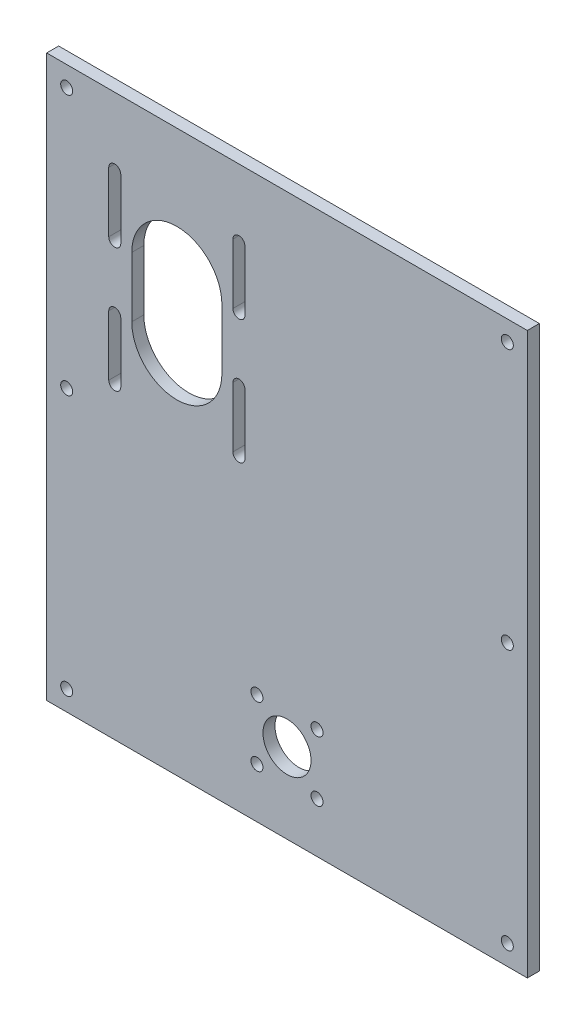
SolidWorks part; units mm, degrees
ref_plane "Plan de face" through (0, 0, 0) normal (0, 0, 1) x (1, 0, 0)
ref_plane "Plan de dessus" through (0, 0, 0) normal (0, 1, 0) x (1, 0, 0)
ref_plane "Plan de droite" through (0, 0, 0) normal (1, 0, 0) x (0, 0, -1)
sketch "Esquisse1" plane through (0, 0, 0) normal (0, 0, 1) x (1, 0, 0)
  line L0 (-27.5, 27.5) -> (-27.5, 42.5) construction
  line L1 (60, -75) -> (-60, -75)
  line L2 (60, -75) -> (60, 75)
  line L3 (60, 75) -> (-60, 75)
  line L4 (-60, -75) -> (-60, 75)
  line L5 (60, -75) -> (-60, 75) construction
  line L6 (60, 75) -> (-60, -75) construction
  line L9 (60, -65) -> (50, -65)
  line L10 (50, -75) -> (50, -65)
  line L13 (-60, -65) -> (-50, -65)
  line L14 (-50, -75) -> (-50, -65)
  line L15 (-38.75, 27.5) -> (-38.75, 42.5)
  line L16 (-16.25, 27.5) -> (-16.25, 42.5)
  line L17 (-43, 43) -> (-43, 58) construction
  line L18 (-44.5, 43) -> (-44.5, 58)
  line L19 (-41.5, 43) -> (-41.5, 58)
  line L20 (-43, 12) -> (-43, 27) construction
  line L21 (-44.5, 12) -> (-44.5, 27)
  line L22 (-41.5, 12) -> (-41.5, 27)
  line L23 (-27.5, 75) -> (-27.5, -75) construction
  line L24 (-27.5, 53.75) -> (-27.5, 16.25) construction
  line L27 (-12, 12) -> (-12, 27) construction
  line L30 (-10.5, 12) -> (-10.5, 27)
  line L31 (-13.5, 12) -> (-13.5, 27)
  line L32 (-12, 43) -> (-12, 58) construction
  line L33 (-10.5, 43) -> (-10.5, 58)
  line L34 (-13.5, 43) -> (-13.5, 58)
  arc A0 (-38.75, 27.5) -> (-16.25, 27.5) centre (-27.5, 27.5) ccw
  arc A1 (-16.25, 42.5) -> (-38.75, 42.5) centre (-27.5, 42.5) ccw
  arc A2 (-44.5, 43) -> (-41.5, 43) centre (-43, 43) ccw
  arc A3 (-41.5, 58) -> (-44.5, 58) centre (-43, 58) ccw
  arc A4 (-44.5, 12) -> (-41.5, 12) centre (-43, 12) ccw
  arc A5 (-41.5, 27) -> (-44.5, 27) centre (-43, 27) ccw
  arc A10 (-10.5, 12) -> (-13.5, 12) centre (-12, 12) cw
  arc A11 (-13.5, 27) -> (-10.5, 27) centre (-12, 27) cw
  arc A12 (-10.5, 43) -> (-13.5, 43) centre (-12, 43) cw
  arc A13 (-13.5, 58) -> (-10.5, 58) centre (-12, 58) cw
  point P0 (0, 0)
  point P14 (-27.5, 35)
  point P21 (-43, 50.5)
  point P28 (-43, 19.5)
  point P37 (-12, 19.5)
  point P44 (-12, 50.5)
  dimension "D13" = 40
  dimension "D1" = 10
  dimension "D2" = 10
  dimension "D3" = 150
  dimension "D4" = 120
  dimension "D5" = 32.5
  dimension "D6" = 15.5
  dimension "D7" = 22.5
  dimension "D8" = 3
  dimension "D9" = 15.5
  dimension "D10" = 15
  dimension "D11" = 3
  dimension "D12" = 31
extrude "Boss.-Extru.1" add sketch "Esquisse1" along normal blind 3 contours L14 L1 L10 L9 L2 L3 L4 L13 A5 L22 A4 L21 A3 L19 A2 L18 A1 L16 A0 L15 L31 A11 L30 A10 L34 A13 L33 A12 region at (1.539, -1.1282, 0)
sketch "Esquisse2" plane through (0, 0, 3) normal (0, 0, 1) x (1, 0, 0)
  line L0 (-55, 75) -> (-55, -65) construction
  line L1 (60, 75) -> (-60, 75) construction
  line L2 (60, -65) -> (50, -65) construction
  line L3 (50, -70) -> (-50, -70) construction
  line L4 (50, -75) -> (50, -65) construction
  line L5 (-50, -75) -> (-50, -65) construction
  line L6 (0, 75) -> (0, -75) construction
  line L7 (50, -75) -> (-50, -75) construction
  circle A0 centre (45, -70) radius 1.5
  circle A3 centre (-55, -60) radius 1.5
  circle A4 centre (-55, 5) radius 1.5
  circle A5 centre (-55, 70) radius 1.5
  circle A9 centre (22.5, -70) radius 1.5
  circle A10 centre (0, -70) radius 1.5
  circle A11 centre (-22.5, -70) radius 1.5
  circle A12 centre (-45, -70) radius 1.5
  circle A13 centre (55, -60) radius 1.5
  circle A14 centre (55, 5) radius 1.5
  circle A15 centre (55, 70) radius 1.5
  dimension "D2" = 3
  dimension "D6" = 3
  dimension "D1" = 5
  dimension "D3" = 5
  dimension "D5" = 5
  dimension "D7" = 5
  dimension "D4" = 5
  dimension "D8" = 3
extrude "Enlèv. mat.-Extru.2" cut sketch "Esquisse2" against normal blind 3
sketch "Esquisse3" plane through (0, 0, 3) normal (0, 0, 1) x (1, 0, 0)
  line L3 (50, -75) -> (-50, -75) construction
  line L4 (0, 75) -> (0, -75) construction
  line L5 (60, 75) -> (-60, 75) construction
  line L6 (-7.5, -37.5) -> (7.5, -37.5) construction
  line L7 (7.5, -57.5) -> (-7.5, -57.5) construction
  line L8 (12.5, -52.5) -> (12.5, -37.5) construction
  line L9 (7.5, -32.5) -> (-7.5, -32.5) construction
  line L10 (-12.5, -52.5) -> (-12.5, -37.5) construction
  line L11 (12.5, -57.5) -> (-12.5, -32.5) construction
  line L12 (12.5, -32.5) -> (-12.5, -57.5) construction
  line L13 (-7.5, -37.5) -> (-7.5, -52.5) construction
  circle A0 centre (0, -45) radius 6
  arc A2 (-7.5, -57.5) -> (-12.5, -52.5) centre (-7.5, -52.5) cw construction
  arc A3 (7.5, -57.5) -> (12.5, -52.5) centre (7.5, -52.5) ccw construction
  arc A4 (12.5, -37.5) -> (7.5, -32.5) centre (7.5, -37.5) ccw construction
  arc A5 (-7.5, -32.5) -> (-12.5, -37.5) centre (-7.5, -37.5) ccw construction
  circle A6 centre (-7.5, -37.5) radius 1.5
  circle A7 centre (7.5, -37.5) radius 1.5
  circle A8 centre (7.5, -52.5) radius 1.5
  circle A9 centre (-7.5, -52.5) radius 1.5
  dimension "D1" = 12
  dimension "D2" = 30
  dimension "D3" = 25
  dimension "D4" = 5
  dimension "D5" = 3
  dimension "D6" = 2
  dimension "D7" = 2
extrude "Enlèv. mat.-Extru.3" cut sketch "Esquisse3" against normal blind 10
sketch "Esquisse4" plane through (0, 0, 3) normal (0, 0, 1) x (1, 0, 0)
  line L0 (-50, -65) -> (50, -65)
  line L1 (50, -65) -> (50, -76.4572)
  line L2 (50, -76.4572) -> (-50, -76.4572)
  line L3 (-50, -76.4572) -> (-50, -65)
extrude "Enlèv. mat.-Extru.4" cut sketch "Esquisse4" against normal blind 10
